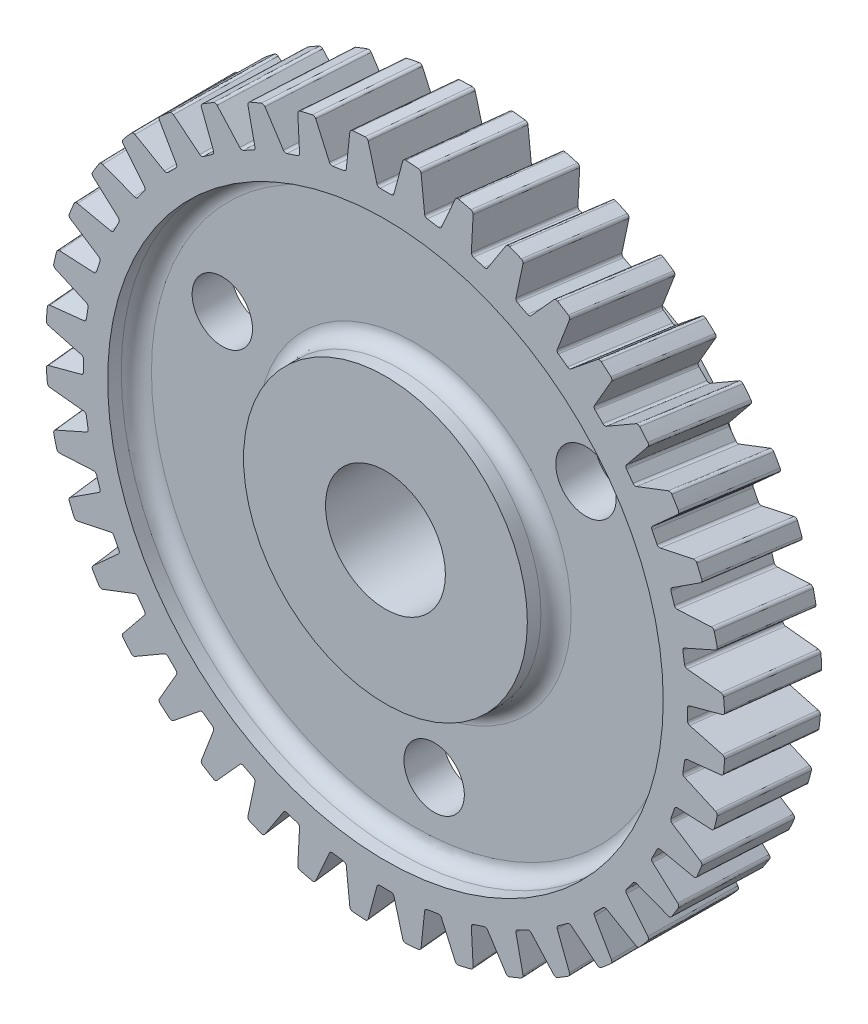
SolidWorks part; units mm, degrees
ref_plane "Front Plane" through (0, 0, 0) normal (0, 0, 1) x (1, 0, 0)
ref_plane "Top Plane" through (0, 0, 0) normal (0, 1, 0) x (1, 0, 0)
ref_plane "Right Plane" through (0, 0, 0) normal (1, 0, 0) x (0, 0, -1)
sketch "Sketch2" plane through (0, 0, 0) normal (1, 0, 0) x (0, 0, -1)
  line L0 (0, 0) -> (0, 22.5) construction
  line L1 (11, 3.9688) -> (-3.2, 3.9687)
  line L2 (-3.2, 3.9687) -> (-3.2, 9.4)
  line L3 (-3.2, 9.4) -> (-1.3, 9.4)
  line L4 (-1.3, 9.4) -> (-1.3, 18.4)
  line L5 (-1.3, 18.4) -> (-3.2, 18.4)
  line L6 (-3.2, 18.4) -> (-3.2, 22.5)
  line L7 (-3.2, 22.5) -> (3.2, 22.5)
  line L8 (3.2, 18.4) -> (3.2, 22.5)
  line L9 (1.3, 18.4) -> (3.2, 18.4)
  line L10 (1.3, 9.4) -> (1.3, 18.4)
  line L11 (3.2, 9.4) -> (1.3, 9.4)
  line L12 (3.2, 9.4) -> (11, 9.4)
  line L13 (11, 9.4) -> (11, 3.9688)
  line L14 (0, 0) -> (14.174, 0) construction
  dimension "D1" = 14.2
  dimension "D2" = 3.2
  dimension "D3" = 4.5
  dimension "D4" = 7.9375
  dimension "D5" = 9.4
  dimension "D6" = 9
  dimension "D7" = 22.5
  dimension "D8" = 6.4
revolve "Revolve1" add sketch "Sketch2" angle 360 about L14
fillet "Fillet1" radius 1 4 edges at (18.4, 0, 1.3) (9.4, 0, 1.3) (9.4, 0, -1.3) (18.4, 0, -1.3)
sketch "Sketch3" plane through (0, 0, 3.2) normal (0, 0, 1) x (1, 0, 0)
  line L0 (0, 22.6922) -> (0, 20) construction
  line L1 (-0.525, 20) -> (0.525, 20)
  line L2 (0.525, 20) -> (1.2464, 22.6922)
  line L3 (1.2464, 22.6922) -> (-1.2464, 22.6922)
  line L4 (-0.525, 20) -> (-1.2464, 22.6922)
  dimension "D1" = 20
  dimension "D2" = 1.05
  dimension "D3" = 15
sketch "Sketch4" plane through (0, 0, 0) normal (0, 1, 0) x (1, 0, 0)
  line L0 (0, -3.2) -> (0.691, 3.2)
  line L1 (1.2464, -3.2) -> (-1.2464, -3.2) construction
  line L2 (22.5, 3.2) -> (-22.5, 3.2) construction
sweep "Cut-Sweep1" cut profiles "Sketch3" path "Sketch4"
pattern_circular "CirPattern1" count 40 over 360 about axis through (0, 0, 3.2) along (0, 0, 1) of "Cut-Sweep1"
fillet "Fillet2" radius 0.2 160 edges at (1.526, 22.4482, 0.0047) (0.8705, 20, 0) (-0.8445, 22.4841, -0.0056) (-2.0045, 22.4105, 0.0047) (-2.2689, 19.8899, 0) (-3.306, 19.7257, 0) (-4.3514, 22.0752, -0.0056) (-5.4856, 21.8211, 0.0047) (-5.3525, 19.2901, 0) (-6.3511, 18.9657, 0) (-7.7512, 21.1227, -0.0056) (-8.8316, 20.6943, 0.0047) (-8.3042, 18.2153, 0) (-9.2398, 17.7386, 0) (-10.9601, 19.6501, -0.0056) (-11.9602, 19.0579, 0.0047) (-11.0515, 16.692, 0) (-11.9009, 16.0748, 0) (-13.8991, 17.6936, -0.0056) (-14.7943, 16.9523, 0.0047) (-13.5266, 14.7577, 0) (-14.2691, 14.0152, 0) (-16.4959, 15.3015, -0.0056) (-17.264, 14.4292, 0.0047) (-15.6687, 12.4599, 0) (-16.2859, 11.6105, 0) (-18.6865, 12.5326, -0.0056) (-19.3087, 11.5509, 0.0047) (-17.4249, 9.8554, 0) (-17.9016, 8.9199, 0) (-20.4169, 9.4551, -0.0056) (-20.878, 8.3882, 0.0047) (-18.7521, 7.0082, 0) (-19.0766, 6.0096, 0) (-21.6447, 6.1448, -0.0056) (-21.9331, 5.0188, 0.0047) (-19.6176, 3.9885, 0) (-19.7818, 2.9514, 0) (-22.3394, 2.6832, -0.0056) (-22.4482, 1.526, 0.0047) (-20, 0.8705, 0) (-20, -0.1795, 0) (-22.4841, -0.8445, -0.0056) (-22.4105, -2.0045, 0.0047) (-19.8899, -2.2689, 0) (-19.7257, -3.306, 0) (-22.0752, -4.3514, -0.0056) (-21.8211, -5.4856, 0.0047) (-19.2901, -5.3525, 0) (-18.9657, -6.3511, 0) (-21.1227, -7.7512, -0.0056) (-20.6943, -8.8316, 0.0047) (-18.2153, -8.3042, 0) (-17.7386, -9.2398, 0) (-19.6501, -10.9601, -0.0056) (-19.0579, -11.9602, 0.0047) (-16.692, -11.0515, 0) (-16.0748, -11.9009, 0) (-17.6936, -13.8991, -0.0056) (-16.9523, -14.7943, 0.0047) (-14.7577, -13.5266, 0) (-14.0152, -14.2691, 0) (-15.3015, -16.4959, -0.0056) (-14.4292, -17.264, 0.0047) (-12.4599, -15.6687, 0) (-11.6105, -16.2859, 0) (-12.5326, -18.6865, -0.0056) (-11.5509, -19.3087, 0.0047) (-9.8554, -17.4249, 0) (-8.9199, -17.9016, 0) (-9.4551, -20.4169, -0.0056) (-8.3882, -20.878, 0.0047) (-7.0082, -18.7521, 0) (-6.0096, -19.0766, 0) (-6.1448, -21.6447, -0.0056) (-5.0188, -21.9331, 0.0047) (-3.9885, -19.6176, 0) (-2.9514, -19.7818, 0) (-2.6832, -22.3394, -0.0056) (-1.526, -22.4482, 0.0047) (-0.8705, -20, 0) (0.1795, -20, 0) (0.8445, -22.4841, -0.0056) (2.0045, -22.4105, 0.0047) (2.2689, -19.8899, 0) (3.306, -19.7257, 0) (4.3514, -22.0752, -0.0056) (5.4856, -21.8211, 0.0047) (5.3525, -19.2901, 0) (6.3511, -18.9657, 0) (7.7512, -21.1227, -0.0056) (8.8316, -20.6943, 0.0047) (8.3042, -18.2153, 0) (9.2398, -17.7386, 0) (10.9601, -19.6501, -0.0056) (11.9602, -19.0579, 0.0047) (11.0515, -16.692, 0) (11.9009, -16.0748, 0) (13.8991, -17.6936, -0.0056) (14.7943, -16.9523, 0.0047) (13.5266, -14.7577, 0) (14.2691, -14.0152, 0) (16.4959, -15.3015, -0.0056) (17.264, -14.4292, 0.0047) (15.6687, -12.4599, 0) (16.2859, -11.6105, 0) (18.6865, -12.5326, -0.0056) (19.3087, -11.5509, 0.0047) (17.4249, -9.8554, 0) (17.9016, -8.9199, 0) (20.4169, -9.4551, -0.0056) (20.878, -8.3882, 0.0047) (18.7521, -7.0082, 0) (19.0766, -6.0096, 0) (21.6447, -6.1448, -0.0056) (21.9331, -5.0188, 0.0047) (19.6176, -3.9885, 0) (19.7818, -2.9514, 0) (22.3394, -2.6832, -0.0056) (22.4482, -1.526, 0.0047) (20, -0.8705, 0) (20, 0.1795, 0) (22.4841, 0.8445, -0.0056) (22.4105, 2.0045, 0.0047) (19.8899, 2.2689, 0) (19.7257, 3.306, 0) (22.0752, 4.3514, -0.0056) (21.8211, 5.4856, 0.0047) (19.2901, 5.3525, 0) (18.9657, 6.3511, 0) (21.1227, 7.7512, -0.0056) (20.6943, 8.8316, 0.0047) (18.2153, 8.3042, 0) (17.7386, 9.2398, 0) (19.6501, 10.9601, -0.0056) (19.0579, 11.9602, 0.0047) (16.692, 11.0515, 0) (16.0748, 11.9009, 0) (17.6936, 13.8991, -0.0056) (16.9523, 14.7943, 0.0047) (14.7577, 13.5266, 0) (14.0152, 14.2691, 0) (15.3015, 16.4959, -0.0056) (14.4292, 17.264, 0.0047) (12.4599, 15.6687, 0) (11.6105, 16.2859, 0) (12.5326, 18.6865, -0.0056) (11.5509, 19.3087, 0.0047) (9.8554, 17.4249, 0) (8.9199, 17.9016, 0) (9.4551, 20.4169, -0.0056) (8.3882, 20.878, 0.0047) (7.0082, 18.7521, 0) (6.0096, 19.0766, 0) (6.1448, 21.6447, -0.0056) (5.0188, 21.9331, 0.0047) (3.9885, 19.6176, 0) (2.9514, 19.7818, 0) (2.6832, 22.3394, -0.0056) (-0.1795, 20, 0)
ref_axis "gear axis" through (0, 0, -11) along (0, 0, 1)
hole_wizard "Ø4.0 (4) Diameter Hole1" positions "Sketch5" profile "Sketch6" hole size "Ø4.0" standard "ISO" end condition through all
sketch "Sketch5" plane through (59.759, -178.203, 3.9366) normal (0, 0, 1) x (1, -0.0054, 0)
  circle A5 centre (-60.718, 177.8786) radius 13.9688
  point P0 (-73.4549, 183.6142)
  point P2 (-49.3823, 186.0412)
  point P4 (-59.3167, 163.9803)
sketch "Sketch6" plane through (-12.7058, 5.8041, 3.9366) normal (1, 0, 0) x (0, -1, 0)
  line L0 (0, 0) -> (0, 14.9366)
  line L1 (0, 14.9366) -> (2, 14.9366)
  line L2 (2, 14.9366) -> (2, 0)
  line L3 (2, 0) -> (0, 0)
  line L4 (0, -6.35) -> (0, 107.95) construction
  dimension "Thru Hole Dia." = 4
  dimension "Thru Hole Depth" = 14.9366
